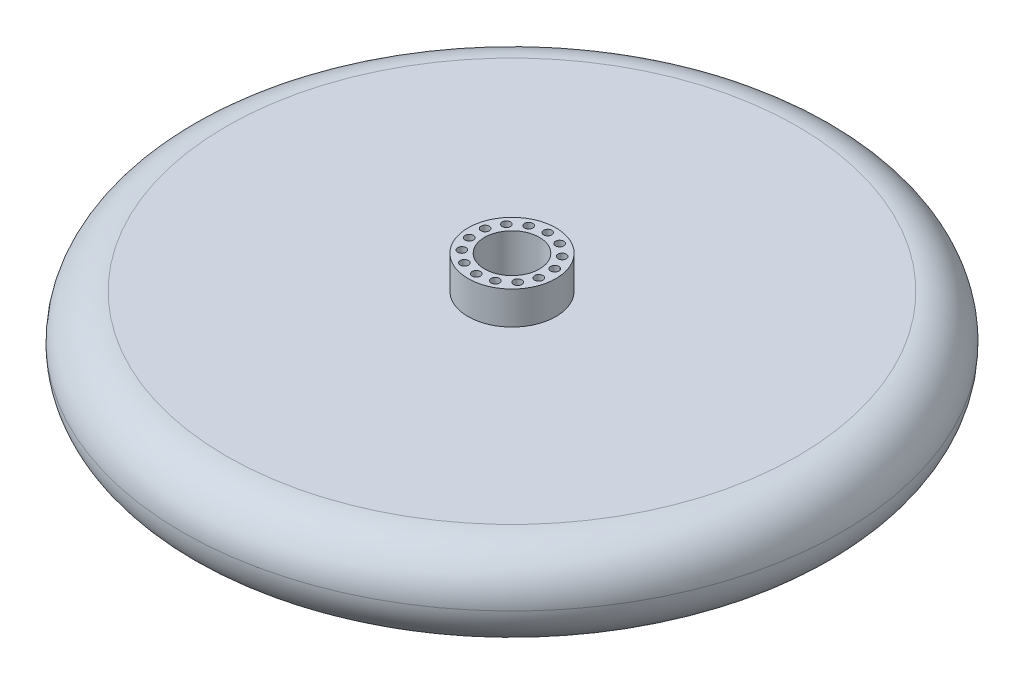
SolidWorks part; units mm, degrees
ref_plane "Front Plane" through (0, 0, 0) normal (0, 0, 1) x (1, 0, 0)
ref_plane "Top Plane" through (0, 0, 0) normal (0, 1, 0) x (1, 0, 0)
ref_plane "Right Plane" through (0, 0, 0) normal (1, 0, 0) x (0, 0, -1)
sketch "Sketch1" plane through (0, 0, 0) normal (0, 1, 0) x (1, 0, 0)
  line L0 (-25.4, 0) -> (25.4, 0) construction
  line L1 (0, 20.6375) -> (0, 25.4) construction
  line L2 (-17.694, 7.9375) -> (17.9359, 7.9375) construction
  line L3 (-17.4625, 25.4) -> (33.3375, 25.4) construction
  line L4 (0, 20.6375) -> (0, 15.875) construction
  circle A1 centre (0, 0) radius 190.5
  circle A2 centre (0, 0) radius 25.4
  circle A3 centre (0, 0) radius 15.875
  circle A4 centre (0, 20.6375) radius 2.3813
  circle A5 centre (8.9543, 18.5937) radius 2.3813
  circle A6 centre (16.135, 12.8673) radius 2.3812
  circle A7 centre (20.1201, 4.5923) radius 2.3813
  circle A8 centre (20.1201, -4.5923) radius 2.3813
  circle A9 centre (16.135, -12.8673) radius 2.3812
  circle A10 centre (8.9543, -18.5937) radius 2.3813
  circle A11 centre (0, -20.6375) radius 2.3813
  circle A12 centre (-8.9543, -18.5937) radius 2.3813
  circle A13 centre (-16.135, -12.8673) radius 2.3813
  circle A14 centre (-20.1201, -4.5923) radius 2.3813
  circle A15 centre (-20.1201, 4.5923) radius 2.3813
  circle A16 centre (-16.135, 12.8673) radius 2.3813
  circle A17 centre (-8.9543, 18.5937) radius 2.3813
  point P44 (0, 0)
  dimension "D1" = 50.8
  dimension "D2" = 31.75
  dimension "D3" = 381
  dimension "D5" = 4.7625
  dimension "D4" = 14
extrude "Boss-Extrude5" add sketch "Sketch1" along normal blind 69.85 and the other way blind 19.05 contours A2 A17 A16 A15 A14 A13 A12 A11 A10 A9 A8 A7 A6 A5 A4 A3 region at (-24.6816, 0, 0)
sketch "Sketch2" plane through (0, -19.05, 0) normal (0, -1, 0) x (-1, 0, 0)
  circle A0 centre (0, 0) radius 190.5
  circle A1 centre (0, 0) radius 25.4
  dimension "D1" = 381
extrude "Boss-Extrude7" add sketch "Sketch2" against normal blind 69.85
sketch "Sketch4" plane through (0, -19.05, 0) normal (0, -1, 0) x (-1, 0, 0)
  circle A0 centre (0, 0) radius 25.4
  circle A1 centre (0, 0) radius 190.5
extrude "Cut-Extrude2" cut sketch "Sketch4" against normal blind 19.05
fillet "Fillet1" radius 25.4 2 edges at (0, 50.8, -190.5) (0, 0, -190.5)
